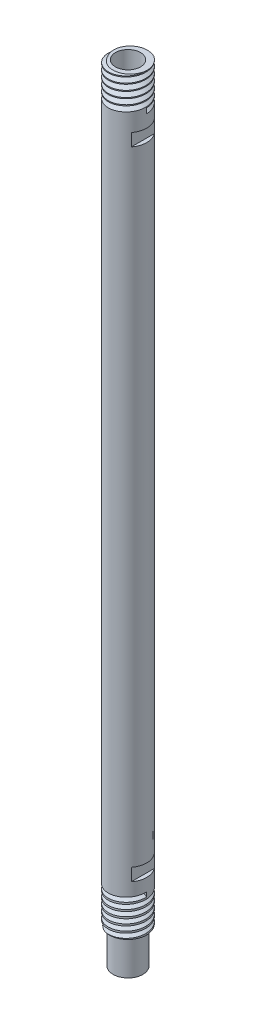
SolidWorks part; units mm, degrees
ref_plane "Front Plane" through (0, 0, 0) normal (0, 0, 1) x (1, 0, 0)
ref_plane "Top Plane" through (0, 0, 0) normal (0, 1, 0) x (1, 0, 0)
ref_plane "Right Plane" through (0, 0, 0) normal (1, 0, 0) x (0, 0, -1)
sketch "Sketch1" plane through (0, 0, 0) normal (0, 1, 0) x (1, 0, 0)
  circle A0 centre (0, 0) radius 4.7625
  circle A1 centre (0, 0) radius 3.175
  dimension "D1" = 9.525
  dimension "D2" = 6.35
extrude "Boss-Extrude1" add sketch "Sketch1" along normal blind 200
sketch "Sketch2" plane through (0, 0, 0) normal (0, 0, 1) x (1, 0, 0)
  line L0 (-4.7625, 0) -> (4.7625, 0) construction
  line L1 (3.7884, 0.3542) -> (3.7884, 9.525)
  line L2 (3.7884, 9.525) -> (4.7625, 9.525)
  line L3 (4.7625, 0) -> (4.7625, 200) construction
  line L4 (4.7625, 9.525) -> (4.7625, 0)
  line L5 (3.7884, 0.3542) -> (3.175, 0)
  line L6 (-3.175, 0) -> (-3.175, 200)
  line L7 (3.175, 200) -> (3.175, 0)
  line L8 (3.175, 200) -> (3.175, 0) construction
  line L9 (3.175, 0) -> (4.7625, 0)
  line L11 (0, 200) -> (0, 0) construction
  dimension "D1" = 3.7884
  dimension "D2" = 30
  dimension "D3" = 9.525
revolve "Cut-Revolve3" cut sketch "Sketch2" angle 360 about axis through (0, 200, 0) along (0, -1, 0)
sketch "Sketch4" plane through (0, 9.525, 0) normal (0, -1, 0) x (1, 0, 0)
  circle A0 centre (0, 0) radius 4.7625 construction
  circle A1 centre (0, 0) radius 4.7625
curve "Helix/Spiral1" pitch 1.5875 height 9.525 radius 4.7625 centre (0, 9.525, 0) axis (0, 1, 0) start towards (1, 0, 0)
sketch "Sketch3" plane through (0, 0, 0) normal (0, 0, 1) x (1, 0, 0)
  line L0 (4.7625, 9.525) -> (3.7884, 8.9626)
  line L1 (3.7884, 0.3542) -> (3.7884, 9.525) construction
  line L2 (3.7884, 8.9626) -> (4.7625, 8.4002)
  line L3 (4.7625, 8.4002) -> (4.7625, 9.525)
  dimension "D1" = 60
sweep "Cut-Sweep1" cut profiles "Sketch3" path "Helix/Spiral1" align with end faces yes
sketch "Sketch6" plane through (0, 200, 0) normal (0, 1, 0) x (1, 0, 0)
  circle A0 centre (0, 0) radius 4.7625 construction
  circle A1 centre (0, 0) radius 4.7625
curve "Helix/Spiral2" pitch 1.5875 height 9.525 radius 4.7625 centre (0, 200, 0) axis (0, -1, 0) start towards (1, 0, 0)
sketch "Sketch5" plane through (0, 0, 0) normal (0, 0, 1) x (1, 0, 0)
  line L0 (4.7625, 201.3315) -> (3.7884, 200.6658)
  line L1 (3.7884, 200.6658) -> (4.7625, 200)
  line L2 (4.7625, 200) -> (4.7625, 201.3315)
  line L3 (0, 200) -> (0, 9.525) construction
  dimension "D1" = 68.703
  dimension "D2" = 3.7884
sweep "Cut-Sweep2" cut profiles "Sketch5" path "Helix/Spiral2" align with end faces yes
sketch "Sketch7" plane through (0, 0, 0) normal (0, 0, 1) x (1, 0, 0)
  line L0 (4.7625, 19.05) -> (4.7625, 190.475) construction
  line L1 (4.7625, 187.3) -> (3.7625, 187.3)
  line L2 (4.7625, 187.3) -> (4.7625, 184.125)
  line L3 (4.7625, 184.125) -> (3.7625, 184.125)
  line L4 (3.7625, 187.3) -> (3.7625, 184.125)
  line L6 (4.7625, 200) -> (-3.3176, 200) construction
  dimension "D1" = 3.175
  dimension "D2" = 12.7
  dimension "D3" = 1
extrude "Cut-Extrude2" cut sketch "Sketch7" against normal through all both and the other way through all
ref_plane "Plane2" through (0, 190.475, 0) normal (0, 1, 0) x (1, 0, 0)
ref_plane "Plane3" through (0, 19.05, 0) normal (0, 1, 0) x (1, 0, 0)
ref_plane "Plane4" through (0, 104.7625, 0) normal (0, 1, 0) x (1, 0, 0)
mirror "Mirror1" about plane through (0, 104.7625, 0) normal (0, 1, 0) of "Cut-Extrude2"
mirror "Mirror2" about plane through (0, 0, 0) normal (1, 0, 0) of "Mirror1", "Cut-Extrude2"
